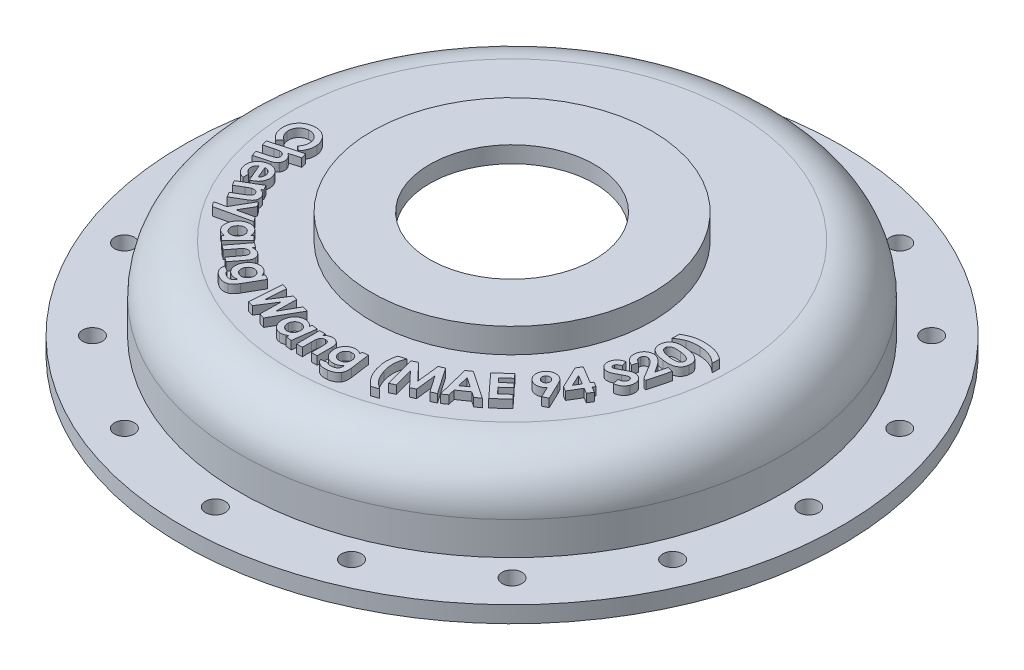
SolidWorks part; units mm, degrees
material "Plain Carbon Steel"
ref_plane "Front Plane" through (0, 0, 0) normal (0, 0, 1) x (1, 0, 0)
ref_plane "Top Plane" through (0, 0, 0) normal (0, 1, 0) x (1, 0, 0)
ref_plane "Right Plane" through (0, 0, 0) normal (1, 0, 0) x (0, 0, -1)
sketch "Sketch3" plane through (0, 0, 0) normal (0, 0, 1) x (1, 0, 0)
  line L0 (0, 0) -> (0, 125.0735) construction
  line L2 (0, 0) -> (200, 0)
  line L3 (0, 0) -> (0, 10)
  line L4 (0, 10) -> (200, 10)
  line L5 (200, 0) -> (200, 10)
  line L6 (0, 60) -> (165, 60)
  line L7 (0, 60) -> (0, 10)
  line L8 (0, 10) -> (165, 10)
  line L9 (165, 60) -> (165, 10)
  line L10 (0, 75) -> (85, 75)
  line L11 (0, 75) -> (0, 60)
  line L12 (0, 60) -> (85, 60)
  line L13 (85, 75) -> (85, 60)
  point P12 (200, 5)
  dimension "D1" = 15
  dimension "D2" = 75
  dimension "D3" = 10
  dimension "D4" = 200
  dimension "D5" = 165
  dimension "D6" = 85
revolve "Revolve1" add sketch "Sketch3" angle 360 about L0 region at (100, 5, 0) region at (82.5, 35, 0) region at (42.5, 67.5, 0) other way angle 360
fillet "Fillet1" radius 30 1 edges at (0, 60, -165)
sketch "Sketch5" plane through (0, 0, 0) normal (0, 1, 0) x (1, 0, 0)
  circle A0 centre (0, 180.0567) radius 6
  dimension "D1" = 12
extrude "Cut-Extrude3" cut sketch "Sketch5" along normal through all
pattern_circular "CirPattern1" count 16 over 360 about axis through (0, 10, 0) along (0, -1, 0) of "Cut-Extrude3"
sketch "Sketch7" plane through (0, 75, 0) normal (0, 1, 0) x (1, 0, 0)
  circle A0 centre (0, 0) radius 50
  dimension "D1" = 100
extrude "Cut-Extrude5" cut sketch "Sketch7" against normal blind 10
shell "Shell7" thickness 10 removed face at (123.0767, 0, -123.0767) removed face at (0, 65, 50)
sketch "Sketch31" plane through (0, 60, 0) normal (0, 1, 0) x (1, 0, 0)
  circle A2 centre (0, 0) radius 125
  circle A3 centre (0, 0) radius 125 construction
  text T0 "<b>Chenyang Wang (MAE 94 S20)</b>" font "Century Gothic" height in points 72
  dimension "D1" = 10
extrude "Boss-Extrude9" add sketch "Sketch31" along normal blind 5
